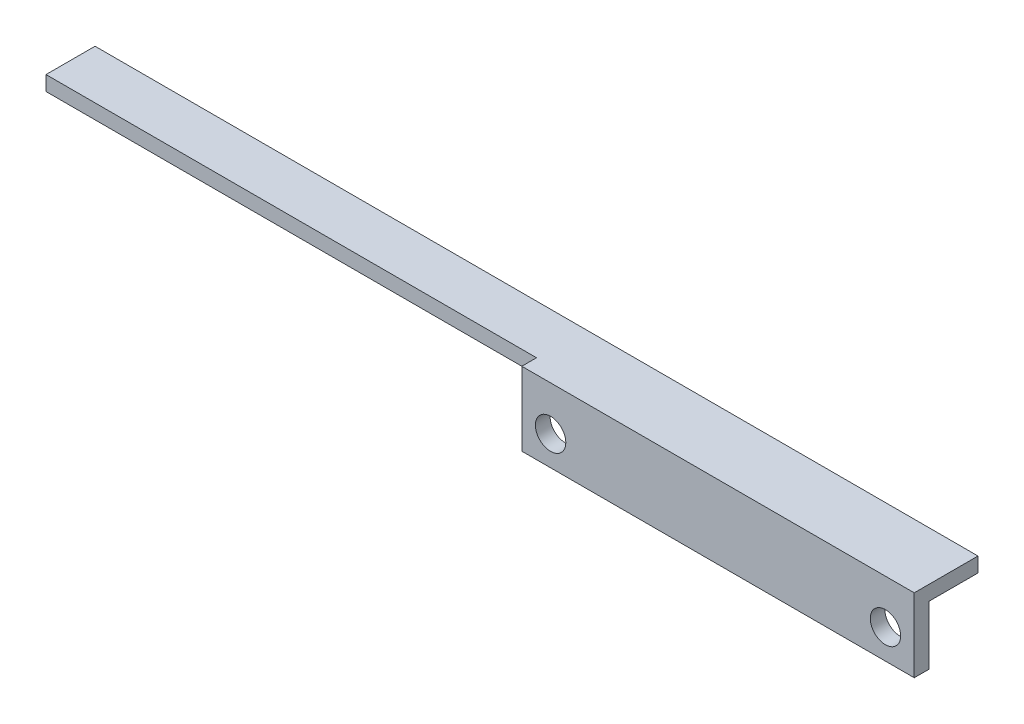
SolidWorks part; units mm, degrees
ref_plane "前视基准面" through (0, 0, 0) normal (0, 0, 1) x (1, 0, 0)
ref_plane "上视基准面" through (0, 0, 0) normal (0, 1, 0) x (1, 0, 0)
ref_plane "右视基准面" through (0, 0, 0) normal (1, 0, 0) x (0, 0, -1)
other "Configuration Table"
sketch "草图1" plane through (0, 0, 0) normal (0, 0, 1) x (1, 0, 0)
  line L1 (20, -3) -> (-20, -3)
  line L2 (20, -3) -> (20, 3)
  line L3 (20, 3) -> (-20, 3)
  line L4 (-20, -3) -> (-20, 3)
  line L5 (20, -3) -> (-20, 3) construction
  line L6 (20, 3) -> (-20, -3) construction
  circle A0 centre (-17.066, 0) radius 1.55
  circle A1 centre (17.066, 0) radius 1.55
  point P0 (0, 0)
  point P6 (-17.066, 0)
  point P7 (17.066, 0)
  dimension "D3" = 3.1
  dimension "D4" = 3.1
  dimension "D1" = 17.066
  dimension "D2" = 17.066
  dimension "D5" = 20
  dimension "D6" = 3
extrude "凸台-拉伸1" add sketch "草图1" along normal blind 1.5
sketch "草图2" plane through (0, 3, 0) normal (0, 1, 0) x (1, 0, 0)
  line L1 (-20, 0) -> (20, 0)
  line L2 (-20, 0) -> (-20, -1.5)
  line L3 (-20, -1.5) -> (20, -1.5)
  line L4 (20, 0) -> (20, -1.5)
extrude "凸台-拉伸2" add sketch "草图2" along normal blind 1.5
sketch "草图3" plane through (0, 0, 1.5) normal (0, 0, 1) x (1, 0, 0)
  line L0 (20, -3) -> (20, 4.5) construction
  line L1 (-20, 4.5) -> (20, 4.5)
  line L2 (-20, 4.5) -> (-20, 3)
  line L3 (-20, 3) -> (20, 3)
  line L4 (20, 4.5) -> (20, 3)
  dimension "D1" = 1.5
sketch "草图4" plane through (0, 0, 0) normal (0, 0, -1) x (-1, 0, 0)
  line L1 (-20, 4.5) -> (20, 4.5)
  line L2 (-20, 4.5) -> (-20, 3)
  line L3 (-20, 3) -> (20, 3)
  line L4 (20, 4.5) -> (20, 3)
extrude "凸台-拉伸3" add sketch "草图4" along normal blind 5
sketch "草图6" plane through (-20, 0, 0) normal (-1, 0, 0) x (0, 0, 1)
  line L1 (-5, 4.5) -> (0, 4.5)
  line L2 (-5, 4.5) -> (-5, 3)
  line L3 (-5, 3) -> (0, 3)
  line L4 (0, 4.5) -> (0, 3)
extrude "凸台-拉伸4" add sketch "草图6" along normal blind 50
